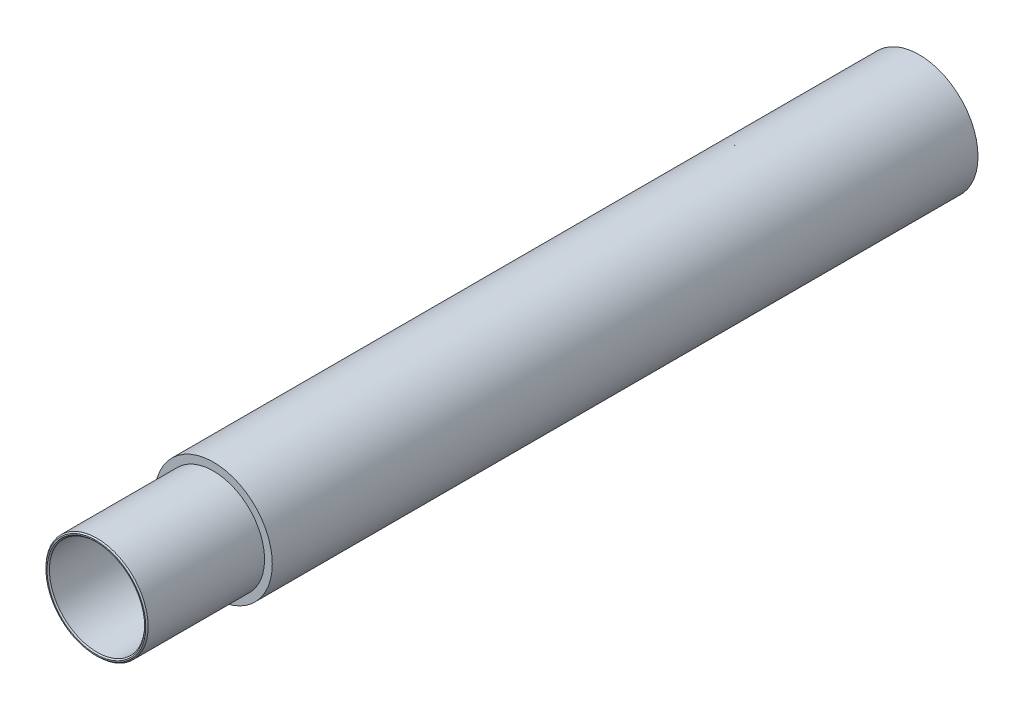
SolidWorks part; units mm, degrees
ref_plane "Front Plane" through (0, 0, 0) normal (0, 0, 1) x (1, 0, 0)
ref_plane "Top Plane" through (0, 0, 0) normal (0, 1, 0) x (1, 0, 0)
ref_plane "Right Plane" through (0, 0, 0) normal (1, 0, 0) x (0, 0, -1)
sketch "Body Tube Converted Sketch" plane through (0, 0, 0) normal (0, 0, 1) x (1, 0, 0)
  circle A2 centre (-72.1213, -196.825) radius 43.65 construction
  circle A3 centre (-72.1213, -196.825) radius 50 construction
  circle A4 centre (-72.1213, -196.825) radius 43.65
  circle A5 centre (-72.1213, -196.825) radius 50
extrude "Body Tube" add sketch "Body Tube Converted Sketch" against normal blind 600
sketch "Upper Couple Sketch" plane through (0, 0, 0) normal (0, 0, -1) x (-1, 0, 0)
  circle A0 centre (72.1213, -196.825) radius 43.65 construction
  circle A1 centre (72.1213, -196.825) radius 43.65
  circle A2 centre (72.1213, -196.825) radius 40.475
  dimension "D1" = 3.175
extrude "Upper Coupler" add sketch "Upper Couple Sketch" along normal blind 50
chamfer "Upper Coupler Chamfer" distance 10 angle 45 1 edges at (-112.5963, -196.825, -50)
sketch "Lower Coupler Sketch" plane through (0, 0, 0) normal (0, 0, 1) x (1, 0, 0)
  circle A1 centre (-72.1213, -196.825) radius 40.475 construction
  circle A4 centre (-72.1213, -196.825) radius 40.475
  circle A7 centre (-72.1213, -196.825) radius 43.45
  circle A8 centre (-72.1213, -196.825) radius 43.45
  dimension "D1" = 0.2
extrude "Lower Coupler" add sketch "Lower Coupler Sketch" along normal blind 100
chamfer "Lower Coupler Chamfer" distance 1 angle 45 2 edges at (-31.6463, -196.825, 100) (-28.6713, -196.825, 100)
